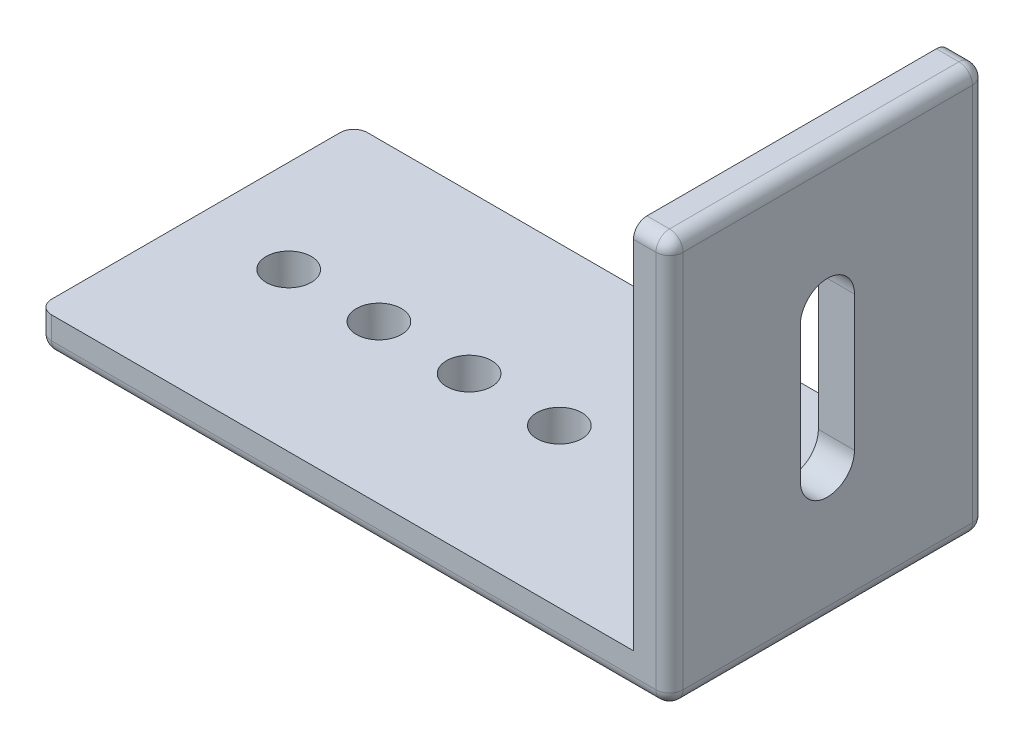
SolidWorks part; units mm, degrees
material "Alloy Steel"
ref_plane "Front Plane" through (0, 0, 0) normal (0, 0, 1) x (1, 0, 0)
ref_plane "Top Plane" through (0, 0, 0) normal (0, 1, 0) x (1, 0, 0)
ref_plane "Right Plane" through (0, 0, 0) normal (1, 0, 0) x (0, 0, -1)
sketch "Sketch1" plane through (0, 0, 0) normal (0, 1, 0) x (1, 0, 0)
  line L1 (-70, -35) -> (70, -35)
  line L2 (-70, -35) -> (-70, 35)
  line L3 (-70, 35) -> (70, 35)
  line L4 (70, -35) -> (70, 35)
  line L5 (-70, -35) -> (70, 35) construction
  line L6 (-70, 35) -> (70, -35) construction
  point P0 (0, 0)
  dimension "D1" = 140
  dimension "D2" = 70
extrude "Base Extrude" add sketch "Sketch1" along normal blind 8
sketch "Sketch2" plane through (70, 0, 0) normal (1, 0, 0) x (0, 0, -1)
  line L1 (-35, 0) -> (35.1581, 0)
  line L2 (-35, 0) -> (-35, 90)
  line L3 (-35, 90) -> (35.1581, 90)
  line L4 (35.1581, 0) -> (35.1581, 90)
  dimension "D1" = 90
extrude "vertical flange" add sketch "Sketch2" against normal blind 8
sketch "Sketch3" plane through (70, 0, 0) normal (1, 0, 0) x (0, 0, -1)
  line L0 (0, 60) -> (0, 30) construction
  line L1 (6, 60) -> (6, 30)
  line L2 (-6, 60) -> (-6, 30)
  line L4 (-35, 0) -> (35.1581, 0) construction
  arc A0 (6, 60) -> (-6, 60) centre (0, 60) ccw
  arc A1 (-6, 30) -> (6, 30) centre (0, 30) ccw
  point P3 (0, 45)
  point P8 (0, 0)
  dimension "D1" = 30
  dimension "D2" = 12
  dimension "D3" = 45
extrude "adujustment slot" cut sketch "Sketch3" against normal through all
sketch "Sketch6" plane through (0, 8, 0) normal (0, 1, 0) x (1, 0, 0)
  line L0 (-49.4277, 0) -> (-29.4277, 0) construction
  circle A0 centre (-49.4277, 0) radius 5
  circle A1 centre (-29.4277, 0) radius 5
  circle A2 centre (-9.4277, 0) radius 5
  circle A3 centre (10.5723, 0) radius 5
  point P3 (0, 0)
  dimension "D1" = 10
  dimension "D3" = 20
  dimension "D2" = 4
extrude "Hole_Pattern" cut sketch "Sketch6" against normal through all both and the other way through all contours A2 | A3 | A1 | A0
fillet "Fillet1" radius 3 4 edges at (70, 0, -0.079) (-4, 0, -35) (-70, 0, 0) (0, 0, 35)
fillet "Fillet2" radius 3 10 edges at (-69.1213, 0.8787, 34.1213) (69.1213, 0.8787, 34.1213) (64.5, 0, -35.1581) (69.1213, 0.8787, -35.1581) (-70, 5.5, 35) (66, 90, -35.1581) (66, 90, 35) (70, 46.5, 35) (70, 46.5, -35.1581) (70, 90, -0.079)
fillet "Fillet3" radius 3 2 edges at (-70, 5.5, -35) (-69.1213, 0.8787, -34.1213)
